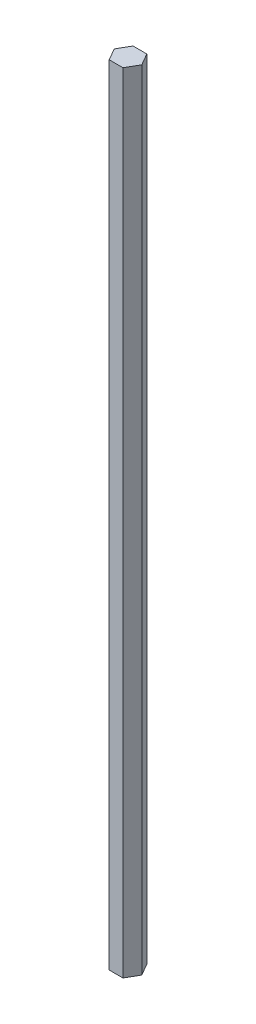
SolidWorks part; units mm, degrees
ref_plane "Front Plane" through (0, 0, 0) normal (0, 0, 1) x (1, 0, 0)
ref_plane "Top Plane" through (0, 0, 0) normal (0, 1, 0) x (1, 0, 0)
ref_plane "Right Plane" through (0, 0, 0) normal (1, 0, 0) x (0, 0, -1)
sketch "Sketch1" plane through (0, 0, 0) normal (0, 1, 0) x (1, 0, 0)
  line L7 (7.3323, 0) -> (3.6662, 6.35)
  line L8 (3.6662, 6.35) -> (-3.6662, 6.35)
  line L9 (-3.6662, 6.35) -> (-7.3323, 0)
  line L10 (-7.3323, 0) -> (-3.6662, -6.35)
  line L11 (-3.6662, -6.35) -> (3.6662, -6.35)
  line L12 (3.6662, -6.35) -> (7.3323, 0)
  circle A0 centre (0, 0) radius 6.35 construction
  dimension "D1" = 12.7
extrude "Boss-Extrude1" add sketch "Sketch1" along normal mid plane 420
ref_axis "Axis1" through (0, 273.0375, 0) along (0, -1, 0)
